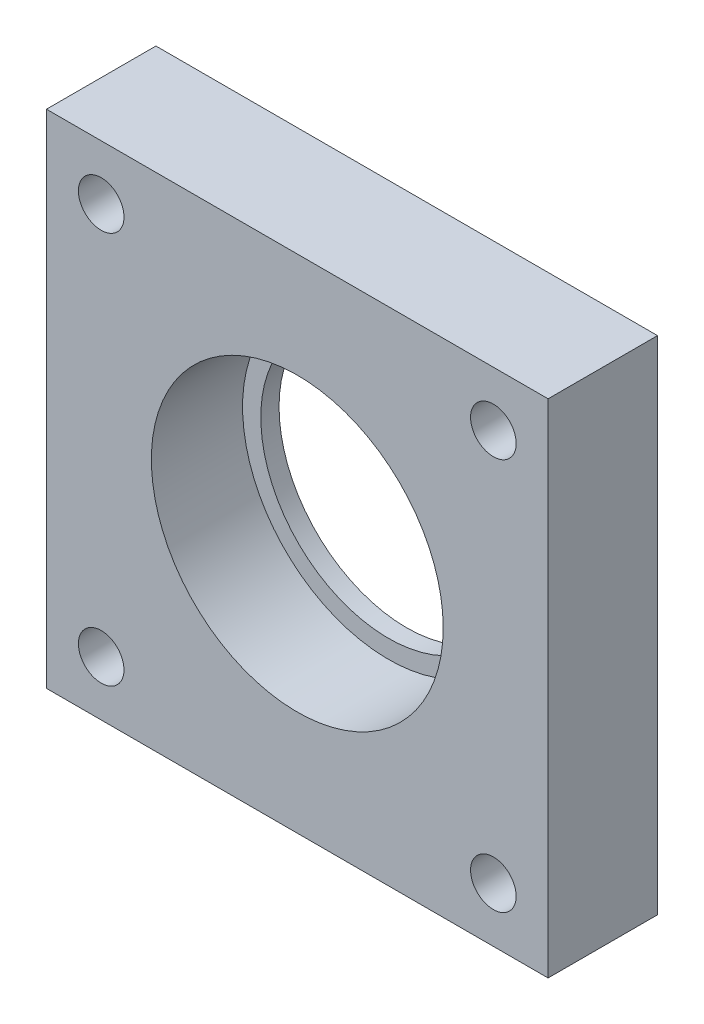
SolidWorks part; units mm, degrees
ref_plane "Piano frontale" through (0, 0, 0) normal (0, 0, 1) x (1, 0, 0)
ref_plane "Piano superiore" through (0, 0, 0) normal (0, 1, 0) x (1, 0, 0)
ref_plane "Piano destro" through (0, 0, 0) normal (1, 0, 0) x (0, 0, -1)
sketch "Schizzo1" plane through (0, 0, 0) normal (0, 0, 1) x (1, 0, 0)
  line L1 (0, 0) -> (55, 0)
  line L2 (0, 0) -> (0, 55)
  line L3 (0, 55) -> (55, 55)
  line L4 (55, 0) -> (55, 55)
  dimension "D1" = 55
  dimension "D2" = 55
extrude "Estrusione-Estrusione1" add sketch "Schizzo1" against normal blind 12
sketch "Schizzo2" plane through (0, 0, 0) normal (0, 0, 1) x (1, 0, 0)
  line L0 (0, 27.5) -> (55, 27.5) construction
  line L1 (0, 55) -> (0, 0) construction
  line L2 (55, 0) -> (55, 55) construction
  circle A0 centre (27.5, 27.5) radius 16
  dimension "D1" = 32
extrude "Taglio-Estrusione1" cut sketch "Schizzo2" against normal blind 10
sketch "Schizzo3" plane through (0, 0, -10) normal (0, 0, 1) x (1, 0, 0)
  line L0 (0, 27.5) -> (55, 27.5) construction
  line L1 (0, 55) -> (0, 0) construction
  line L2 (55, 0) -> (55, 55) construction
  circle A0 centre (27.5, 27.5) radius 14
  dimension "D1" = 28
extrude "Taglio-Estrusione2" cut sketch "Schizzo3" against normal blind 10
sketch "Schizzo4" plane through (0, 0, 0) normal (0, 0, 1) x (1, 0, 0)
  line L0 (0, 27.5) -> (55, 27.5) construction
  line L1 (0, 55) -> (0, 0) construction
  line L2 (55, 0) -> (55, 55) construction
  line L3 (0, 55) -> (0, 27.5) construction
  line L4 (55, 55) -> (0, 55) construction
  line L5 (27.5, 55) -> (27.5, 0) construction
  line L6 (0, 0) -> (55, 0) construction
  line L7 (0, 55) -> (27.5, 55) construction
  line L8 (6, 55) -> (6, 27.5) construction
  line L9 (0, 49) -> (27.5, 49) construction
  circle A0 centre (6, 49) radius 2.5
  circle A1 centre (49, 49) radius 2.5
  circle A2 centre (49, 6) radius 2.5
  circle A3 centre (6, 6) radius 2.5
  point P16 (27.5, 27.5)
  dimension "D3" = 5
  dimension "D4" = 30.4056
  dimension "D1" = 6
  dimension "D2" = 6
extrude "Taglio-Estrusione3" cut sketch "Schizzo4" against normal blind 12
